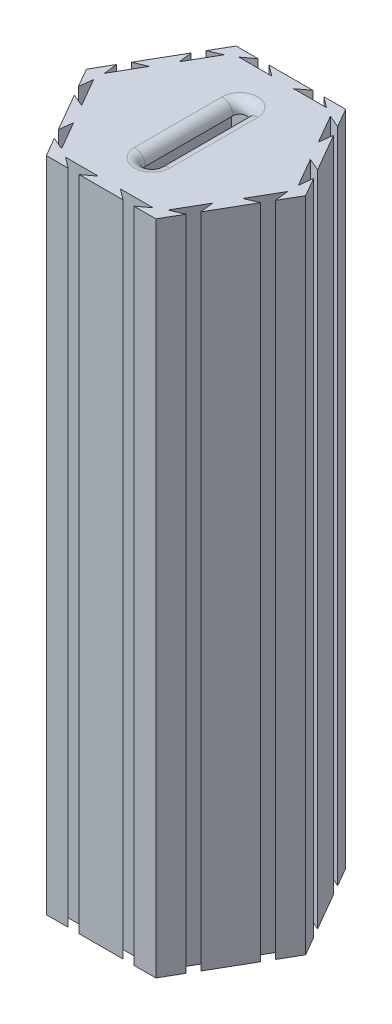
SolidWorks part; units mm, degrees
ref_plane "Front Plane" through (0, 0, 0) normal (0, 0, 1) x (1, 0, 0)
ref_plane "Top Plane" through (0, 0, 0) normal (0, 1, 0) x (1, 0, 0)
ref_plane "Right Plane" through (0, 0, 0) normal (1, 0, 0) x (0, 0, -1)
sketch "Sketch1" plane through (0, 0, 0) normal (0, 1, 0) x (1, 0, 0)
  line L1 (40, 0) -> (20, 34.641)
  line L2 (20, 34.641) -> (-20, 34.641)
  line L3 (-20, 34.641) -> (-40, 0)
  line L4 (-40, 0) -> (-20, -34.641)
  line L5 (-20, -34.641) -> (20, -34.641)
  line L6 (20, -34.641) -> (40, 0)
  circle A0 centre (0, 0) radius 40 construction
  dimension "D1" = 80
extrude "Boss-Extrude1" add sketch "Sketch1" along normal blind 240 contours L1 L2 L3 L4 L5 L6
shell "Shell1" thickness 4
sketch "Sketch2" plane through (0, 0, 0) normal (0, -1, 0) x (1, 0, 0)
  line L0 (-20, 34.641) -> (20, -34.641)
  line L1 (20, 34.641) -> (-20, -34.641)
  line L2 (-40, 0) -> (40, 0)
  line L3 (-12, 34.641) -> (-16, 31.641)
  line L4 (-20, 34.641) -> (20, 34.641) construction
  line L5 (-16, 31.641) -> (-4, 31.641)
  line L6 (-4, 31.641) -> (-8, 34.641)
  line L7 (-12, 34.641) -> (-8, 34.641)
  line L8 (0, 34.641) -> (0, -34.641)
  line L9 (20, -34.641) -> (-20, -34.641) construction
  line L10 (-30, 17.3205) -> (30, -17.3205)
  line L11 (-40, 0) -> (-20, 34.641) construction
  line L12 (40, 0) -> (20, -34.641) construction
  line L13 (30, 17.3205) -> (-30, -17.3205)
  line L14 (20, 34.641) -> (40, 0) construction
  line L15 (-20, -34.641) -> (-40, 0) construction
  line L16 (-24, 27.7128) -> (-19.4019, 29.6769)
  line L17 (-19.4019, 29.6769) -> (-25.4019, 19.2846)
  line L18 (-25.4019, 19.2846) -> (-26, 24.2487)
  line L19 (-24, 27.7128) -> (-26, 24.2487)
  line L20 (12, 34.641) -> (16, 31.641)
  line L21 (16, 31.641) -> (4, 31.641)
  line L22 (4, 31.641) -> (8, 34.641)
  line L23 (12, 34.641) -> (8, 34.641)
  line L24 (24, 27.7128) -> (26, 24.2487)
  line L25 (25.4019, 19.2846) -> (26, 24.2487)
  line L26 (19.4019, 29.6769) -> (25.4019, 19.2846)
  line L27 (24, 27.7128) -> (19.4019, 29.6769)
  line L28 (36, 6.9282) -> (35.4019, 1.9641)
  line L29 (35.4019, 1.9641) -> (29.4019, 12.3564)
  line L30 (29.4019, 12.3564) -> (34, 10.3923)
  line L31 (36, 6.9282) -> (34, 10.3923)
  line L32 (36, -6.9282) -> (34, -10.3923)
  line L33 (29.4019, -12.3564) -> (34, -10.3923)
  line L34 (35.4019, -1.9641) -> (29.4019, -12.3564)
  line L35 (36, -6.9282) -> (35.4019, -1.9641)
  line L36 (19.4019, -29.6769) -> (25.4019, -19.2846)
  line L37 (25.4019, -19.2846) -> (26, -24.2487)
  line L38 (24, -27.7128) -> (26, -24.2487)
  line L39 (24, -27.7128) -> (19.4019, -29.6769)
  line L40 (12, -34.641) -> (16, -31.641)
  line L41 (12, -34.641) -> (8, -34.641)
  line L42 (4, -31.641) -> (8, -34.641)
  line L43 (16, -31.641) -> (4, -31.641)
  line L44 (-12, -34.641) -> (-8, -34.641)
  line L45 (-4, -31.641) -> (-8, -34.641)
  line L46 (-16, -31.641) -> (-4, -31.641)
  line L47 (-12, -34.641) -> (-16, -31.641)
  line L48 (-24, -27.7128) -> (-19.4019, -29.6769)
  line L49 (-25.4019, -19.2846) -> (-26, -24.2487)
  line L50 (-24, -27.7128) -> (-26, -24.2487)
  line L51 (-19.4019, -29.6769) -> (-25.4019, -19.2846)
  line L52 (-36, -6.9282) -> (-34, -10.3923)
  line L53 (-29.4019, -12.3564) -> (-34, -10.3923)
  line L54 (-35.4019, -1.9641) -> (-29.4019, -12.3564)
  line L55 (-36, -6.9282) -> (-35.4019, -1.9641)
  line L56 (-36, 6.9282) -> (-35.4019, 1.9641)
  line L57 (-35.4019, 1.9641) -> (-29.4019, 12.3564)
  line L58 (-29.4019, 12.3564) -> (-34, 10.3923)
  line L59 (-36, 6.9282) -> (-34, 10.3923)
  line M51 (40, 0) -> (20, 34.641)
  line M52 (20, 34.641) -> (-20, 34.641)
  line M53 (-20, 34.641) -> (-40, 0)
  line M54 (-40, 0) -> (-20, -34.641)
  line M55 (-20, -34.641) -> (20, -34.641)
  line M56 (20, -34.641) -> (40, 0)
  dimension "D1" = 12
  dimension "D2" = 3
  dimension "D3" = 5
  dimension "D4" = 5
  dimension "D5" = 8
extrude "Cut-Extrude1" cut sketch "Sketch2" against normal through all contours L18 L17 L16 M53 | L22 L21 L20 M52 | L27 L26 L25 M51 | L30 L29 L28 M51 | L35 L34 L33 M56 | L39 L37 L36 M56 | L40 L43 L42 M55 | L47 L45 L46 M55 | L48 L51 L49 M54 | L55 L53 L54 M54 | L57 L58 L56 M53 | L5 L6 L7 L3 region at (-23.4845, 0, 25.1058) region at (10, 0, -32.891) region at (23.4845, 0, -25.1058) region at (23.4845, 0, 25.1058) region at (10, 0, 32.891) region at (-23.4845, 0, -25.1058) region at (-10, 0, -32.891) region at (-33.4845, 0, 7.7853) region at (-33.4845, 0, -7.7853) region at (33.4845, 0, 7.7853) region at (33.4845, 0, -7.7853)
sketch "Sketch3" plane through (0, 240, 0) normal (0, 1, 0) x (1, 0, 0)
  line L0 (0, 16) -> (0, -16) construction
  line L1 (2.5, 16) -> (2.5, -16)
  line L2 (-2.5, 16) -> (-2.5, -16)
  line L3 (-40, 0) -> (40, 0)
  arc A0 (2.5, 16) -> (-2.5, 16) centre (0, 16) ccw
  arc A1 (-2.5, -16) -> (2.5, -16) centre (0, -16) ccw
  point P0 (0, -18.5)
  point P3 (0, 0)
  dimension "D2" = 32
  dimension "D1" = 0
  dimension "D3" = 5
extrude "Cut-Extrude2" cut sketch "Sketch3" against normal up to next contours L1 A0 L2 L3 | L2 A1 L1 L3 region at (0, 240, -8.9904) region at (0, 240, 8.9904)
fillet "Fillet1" radius 4 4 edges at (0, 240, -18.5) (-2.5, 240, 0) (0, 240, 18.5) (2.5, 240, 0)
